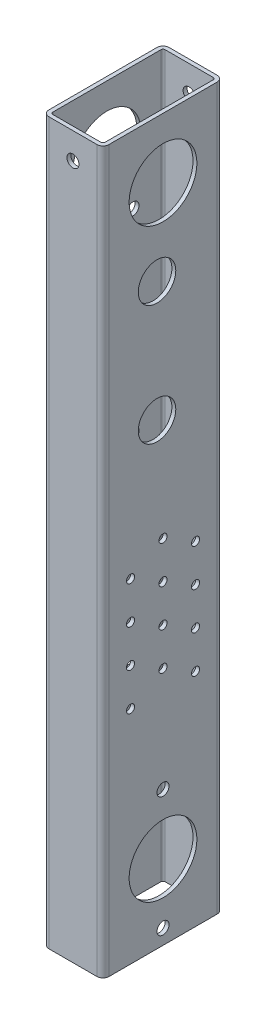
SolidWorks part; units mm, degrees
material "6061-T6 (SS)"
ref_plane "Front Plane" through (0, 0, 0) normal (0, 0, 1) x (1, 0, 0)
ref_plane "Top Plane" through (0, 0, 0) normal (0, 1, 0) x (1, 0, 0)
ref_plane "Right Plane" through (0, 0, 0) normal (1, 0, 0) x (0, 0, -1)
sketch "Sketch1" plane through (0, 0, 0) normal (0, 1, 0) x (1, 0, 0)
  line L1 (10.16, -25.4) -> (-10.16, -25.4)
  line L2 (12.7, -22.86) -> (12.7, 22.86)
  line L3 (10.16, 25.4) -> (-10.16, 25.4)
  line L4 (-12.7, -22.86) -> (-12.7, 22.86)
  line L5 (12.7, -25.4) -> (-12.7, 25.4) construction
  line L6 (12.7, 25.4) -> (-12.7, -25.4) construction
  arc A0 (-10.16, -25.4) -> (-12.7, -22.86) centre (-10.16, -22.86) cw
  arc A1 (10.16, -25.4) -> (12.7, -22.86) centre (10.16, -22.86) ccw
  arc A2 (12.7, 22.86) -> (10.16, 25.4) centre (10.16, 22.86) ccw
  arc A3 (-10.16, 25.4) -> (-12.7, 22.86) centre (-10.16, 22.86) ccw
  point P0 (0, 0)
  dimension "D3" = 2.54
  dimension "D1" = 25.4
  dimension "D2" = 50.8
extrude "Extrude-Thin1" add sketch "Sketch1" along normal blind 222.25 and the other way blind 82.55 thin thin type one direction reverse wall 1.651
sketch "Sketch2" plane through (-12.7, 0, 0) normal (-1, 0, 0) x (0, 0, 1)
  line L0 (2.54, 161.9426) -> (2.54, 12.7) construction
  line L4 (9.2075, 161.9426) -> (9.2075, 12.7)
  line L5 (-4.1275, 161.9426) -> (-4.1275, 12.7)
  line L6 (2.54, 25.4) -> (2.54, 149.2426) construction
  arc A2 (9.2075, 161.9426) -> (-4.1275, 161.9426) centre (2.54, 161.9426) ccw
  arc A3 (-4.1275, 12.7) -> (9.2075, 12.7) centre (2.54, 12.7) ccw
  point P3 (2.54, 87.3213)
  dimension "D5" = 13.335
  dimension "D2" = 12.7
  dimension "D1" = 12.7
extrude "Cut-Extrude1" cut sketch "Sketch2" against normal up to next
sketch "Sketch5" plane through (12.7, 0, 0) normal (1, 0, 0) x (0, 0, -1)
  circle A2 centre (-2.54, 161.9426) radius 7.9375
  circle A3 centre (-2.54, 111.1426) radius 6.6675 construction
  circle A4 centre (-2.54, 111.1426) radius 6.6675 construction
  circle A5 centre (-2.54, 161.9426) radius 6.6675 construction
  circle A6 centre (-2.54, 161.9426) radius 6.6675 construction
  circle A7 centre (-2.54, 111.1426) radius 7.9375
  dimension "D1" = 15.875
extrude "Cut-Extrude4" cut sketch "Sketch5" against normal up to next
sketch "Sketch4" plane through (-12.7, 0, 0) normal (1, 0, 0) x (0, 0, -1)
  circle A12 centre (11.049, 4.7713) radius 2.5527
  circle A13 centre (-16.129, 4.7713) radius 2.5527
  circle A14 centre (-16.129, 87.3213) radius 2.5527
  circle A15 centre (11.049, 87.3213) radius 2.5527
  circle A16 centre (-16.129, 169.8713) radius 2.5527
  circle A17 centre (11.049, 169.8713) radius 2.5527
  dimension "D1" = 5.1054
extrude "Cut-Extrude3" cut sketch "Sketch4" along normal up to surface (1.651 mm away) up to face at (-11.049, 87.3213, 2.54)
sketch "Sketch6" plane through (12.7, 0, 0) normal (1, 0, 0) x (0, 0, -1)
  line L0 (25.4, -82.55) -> (25.4, 222.25) construction
  circle A0 centre (0, -50.8) radius 14.3256
  circle A1 centre (0, 196.85) radius 14.3256
  dimension "D1" = 28.6512
  dimension "D2" = 25.4
  dimension "D3" = 50.8
  dimension "D4" = 247.65
extrude "Cut-Extrude5" cut sketch "Sketch6" against normal through all
hole_wizard "#10 Clearance Hole1" positions "Sketch8" profile "Sketch9" hole size "#10" standard "ANSI Inch" end condition through all
sketch "Sketch8" plane through (12.7, 0, 0) normal (1, 0, 0) x (0, 0, -1)
  circle A0 centre (0, -50.8) radius 25.4 construction
  point P0 (0, -25.4)
  point P11 (0, -76.2)
  dimension "D1" = 50.8
sketch "Sketch9" plane through (12.7, -25.4, 0) normal (0, 1, 0) x (0, 0, -1)
  line L0 (0, 0) -> (0, 25.4)
  line L1 (0, 25.4) -> (2.5527, 25.4)
  line L2 (2.5527, 25.4) -> (2.5527, 0)
  line L5 (2.5527, 0) -> (0, 0)
  line L11 (0, -6.35) -> (0, 107.95) construction
  dimension "Thru Hole Dia." = 5.1054
  dimension "Thru Hole Depth" = 25.4
hole_wizard "1/8 (0.135) Diameter Hole1" positions "Sketch10" profile "Sketch11" hole size "1/8" standard "ANSI Inch" end condition up to next
sketch "Sketch10" plane through (12.7, 0, 0) normal (1, 0, 0) x (0, 0, -1)
  point P39 (0, 66.5303)
  point P42 (13.7482, 58.5928)
  point P45 (-13.7482, 58.5928)
  point P48 (0, 50.6553)
  point P51 (0, 34.7803)
  point P54 (-13.7482, 42.7178)
  point P57 (13.7482, 26.8428)
  point P60 (13.7482, 42.7178)
  point P63 (0, 18.9053)
  point P66 (-13.7482, 26.8428)
  point P69 (-13.7482, 10.9678)
  point P72 (13.7482, 10.9678)
sketch "Sketch11" plane through (12.7, 66.5303, 0) normal (0, 1, 0) x (0, 0, -1)
  line L0 (0, 0) -> (0, 1.651)
  line L1 (0, 1.651) -> (1.7145, 1.651)
  line L2 (1.7145, 1.651) -> (1.7145, 0)
  line L5 (1.7145, 0) -> (0, 0)
  line L11 (0, -6.35) -> (0, 107.95) construction
  dimension "Thru Hole Dia." = 3.429
  dimension "Thru Hole Depth" = 1.651
hole_wizard "1/8 (0.135) Diameter Hole2" positions "Sketch12" profile "Sketch13" hole size "1/8" standard "ANSI Inch" end condition up to next
sketch "Sketch12" plane through (-12.7, 0, 0) normal (-1, 0, 0) x (0, 0, 1)
  point P0 (17.399, 63.3553)
  point P3 (17.399, 53.8303)
  point P6 (17.399, 44.3053)
  point P9 (17.399, 34.7803)
  point P12 (17.399, 25.2553)
  point P15 (17.399, 15.7303)
sketch "Sketch13" plane through (-12.7, 63.3553, 17.399) normal (0, 1, 0) x (0, 0, 1)
  line L0 (0, 0) -> (0, 1.651)
  line L1 (0, 1.651) -> (1.7145, 1.651)
  line L2 (1.7145, 1.651) -> (1.7145, 0)
  line L5 (1.7145, 0) -> (0, 0)
  line L11 (0, -6.35) -> (0, 107.95) construction
  dimension "Thru Hole Dia." = 3.429
  dimension "Thru Hole Depth" = 1.651
hole_wizard "#10 Clearance Hole2" positions "Sketch14" profile "Sketch15" hole size "#10" standard "ANSI Inch" end condition through all
sketch "Sketch14" plane through (0, 0, -25.4) normal (0, 0, -1) x (-1, 0, 0)
  point P0 (0, 211.1375)
sketch "Sketch15" plane through (0, 211.1375, -25.4) normal (1, 0, 0) x (0, 1, 0)
  line L0 (0, 0) -> (0, 50.8)
  line L1 (0, 50.8) -> (2.5527, 50.8)
  line L2 (2.5527, 50.8) -> (2.5527, 0)
  line L5 (2.5527, 0) -> (0, 0)
  line L11 (0, -6.35) -> (0, 107.95) construction
  dimension "Thru Hole Dia." = 5.1054
  dimension "Thru Hole Depth" = 50.8
move or copy body "Body-Move/Copy1" [suppressed] bodies to move or copy 110 parameters "D1"=0, "D2"=0, "D3"=0
